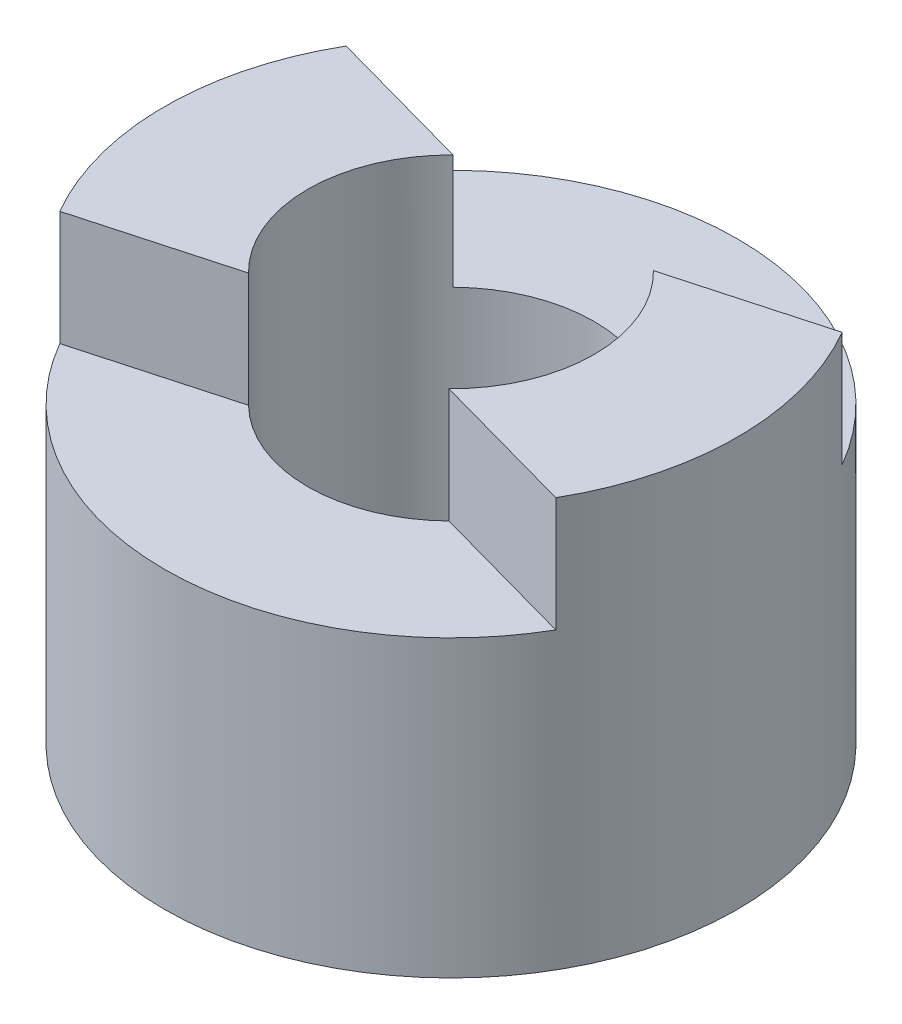
SolidWorks part; units mm, degrees
ref_plane "Front Plane" through (0, 0, 0) normal (0, 0, 1) x (1, 0, 0)
ref_plane "Top Plane" through (0, 0, 0) normal (0, 1, 0) x (1, 0, 0)
ref_plane "Right Plane" through (0, 0, 0) normal (1, 0, 0) x (0, 0, -1)
sketch "Sketch1" plane through (0, 0, 0) normal (0, 1, 0) x (1, 0, 0)
  circle A0 centre (0, 0) radius 35
  circle A1 centre (0, 0) radius 17.5
  dimension "D1" = 70
  dimension "D2" = 35
extrude "Boss-Extrude1" add sketch "Sketch1" along normal blind 50
sketch "Sketch2" plane through (0, 50, 0) normal (0, 1, 0) x (1, 0, 0)
  line L0 (0, 0) -> (45.0155, 0) construction
  line L1 (0, 0) -> (0, -60.2355) construction
  line L2 (12.2474, -12.5) -> (30.3109, -17.5)
  line L3 (-12.2474, -12.5) -> (-30.3109, -17.5)
  circle A0 centre (0, 0) radius 35 construction
  arc A1 (-30.3109, -17.5) -> (30.3109, -17.5) centre (0, 0) ccw
  circle A2 centre (0, 0) radius 17.5 construction
  arc A3 (-12.2474, -12.5) -> (12.2474, -12.5) centre (0, 0) ccw
  point P4 (13.4785, -11.1615)
  point P8 (0, 0)
  point P14 (0, 0)
  point P15 (0, 0)
  point P16 (0, 0)
  point P17 (15.1554, -8.75)
  point P18 (12.8785, -11.8488)
  point P19 (0, 0)
  dimension "D1" = 35
  dimension "D2" = 25
extrude "Cut-Extrude1" cut sketch "Sketch2" against normal offset from surface (14 mm away) 36 up to face at (0, 0, 35)
ref_axis "Axis1" through (0, 50, 0) along (0, -1, 0)
mirror "Mirror1" about plane through (0, 0, 0) normal (0, 0, 1) of "Cut-Extrude1"
